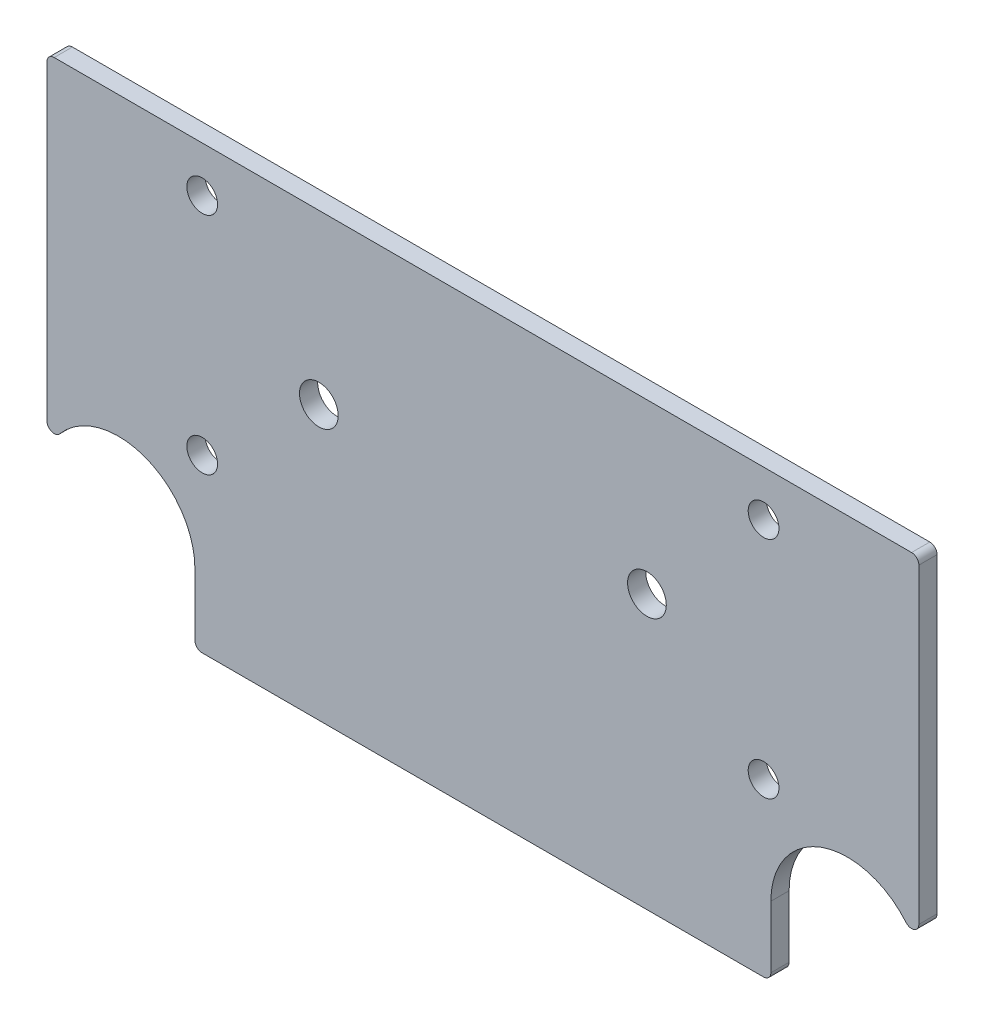
SolidWorks part; units mm, degrees
material "PC High Viscosity"
ref_plane "Front Plane" through (0, 0, 0) normal (0, 0, 1) x (1, 0, 0)
ref_plane "Top Plane" through (0, 0, 0) normal (0, 1, 0) x (1, 0, 0)
ref_plane "Right Plane" through (0, 0, 0) normal (1, 0, 0) x (0, 0, -1)
sketch "Sketch1" plane through (0, 0, 0) normal (0, 0, 1) x (1, 0, 0)
  line L0 (127, 0) -> (-127, 0) construction
  line L1 (101.6, -357.1875) -> (101.6, 357.1875) construction
  line L2 (152.4, 0) -> (152.4, 357.1875) construction
  line L3 (-101.6, -357.1875) -> (-101.6, 357.1875) construction
  line L4 (-152.4, -357.1875) -> (-152.4, 357.1875) construction
  line L5 (101.6, 59.0332) -> (-101.6, 262.2332) construction
  line L6 (101.6, 94.9543) -> (-101.6, 298.1543) construction
  line L7 (0, 196.5543) -> (0, 160.6332) construction
  line L8 (0, 178.5938) -> (152.4, 178.5938) construction
  line L9 (105.003, 12.7) -> (-105.003, 12.7) construction
  line L10 (105.003, -12.7) -> (-105.003, -12.7) construction
  line L11 (-101.6, 59.0332) -> (101.6, 262.2332) construction
  line L12 (-101.6, 94.9543) -> (101.6, 298.1543) construction
  line L13 (152.4, 0) -> (152.4, -357.1875) construction
  line L14 (-101.6, -94.9543) -> (101.6, -298.1543) construction
  line L15 (-101.6, -59.0332) -> (101.6, -262.2332) construction
  line L16 (101.6, -94.9543) -> (-101.6, -298.1543) construction
  line L17 (101.6, -59.0332) -> (-101.6, -262.2332) construction
  line L18 (-179.07, -25.4) -> (-179.07, 128.4583)
  line L19 (-179.07, 128.4583) -> (179.07, 128.4583)
  line L20 (179.07, 128.4583) -> (179.07, -25.4)
  line L21 (179.07, -25.4) -> (153.67, -25.4)
  line L22 (153.67, -25.4) -> (153.67, -1.27)
  line L23 (100.33, -1.27) -> (100.33, -25.4)
  line L24 (100.33, -25.4) -> (-100.33, -25.4)
  line L25 (-100.33, -25.4) -> (-100.33, -1.27)
  line L26 (-153.67, -1.27) -> (-153.67, -25.4)
  line L27 (-179.07, -25.4) -> (-153.67, -25.4)
  circle A0 centre (-127, 0) radius 25.4 construction
  circle A1 centre (127, 0) radius 25.4 construction
  circle A2 centre (-127, 357.1875) radius 25.4 construction
  circle A3 centre (127, 357.1875) radius 25.4 construction
  arc A4 (100.33, -1.27) -> (153.67, -1.27) centre (127, -1.27) cw
  arc A5 (-100.33, -1.27) -> (-153.67, -1.27) centre (-127, -1.27) ccw
  circle A6 centre (96.139, 108.1383) radius 5.461 construction
  point P23 (0, 178.5938)
  point P33 (101.6, 0)
  point P37 (-152.4, 0)
  point P38 (-101.6, 0)
  point P53 (127, 25.4)
  point P54 (127, 25.4)
  dimension "D2" = 50.8
  dimension "D7" = 26.67
  dimension "D9" = 25.4
  dimension "D10" = 10.922
  dimension "D1" = 254
  dimension "D3" = 357.1875
  dimension "D4" = 25.4
  dimension "D5" = 45
  dimension "D6" = 25.4
  dimension "D8" = 25.4
  dimension "D11" = 20.32
extrude "Boss-Extrude1" add sketch "Sketch1" along normal blind 6.35
sketch "Sketch7" plane through (0, 0, 0) normal (0, 0, -1) x (-1, 0, 0)
  line L0 (-151.892, 128.4583) -> (-151.892, 8.3048)
  line L1 (-152.4, 0) -> (-152.4, 357.1875) construction
  line L2 (-179.07, 128.4583) -> (179.07, 128.4583) construction
  line L3 (0, -25.4) -> (0, 128.4583) construction
  line L4 (100.33, -25.4) -> (-100.33, -25.4) construction
  line L5 (-151.892, 128.4583) -> (-179.07, 128.4583)
  line L6 (-179.07, 128.4583) -> (-179.07, -25.4)
  line L7 (-179.07, -25.4) -> (-153.67, -25.4)
  line L8 (-153.67, -25.4) -> (-153.67, -1.27)
  line L9 (153.67, -25.4) -> (153.67, -1.27)
  line L10 (179.07, -25.4) -> (153.67, -25.4)
  line L11 (179.07, 128.4583) -> (179.07, -25.4)
  line L12 (151.892, 128.4583) -> (179.07, 128.4583)
  line L13 (151.892, 128.4583) -> (151.892, 8.3048)
  arc A0 (-100.33, -1.27) -> (-153.67, -1.27) centre (-127, -1.27) ccw construction
  arc A1 (-153.67, -1.27) -> (-151.892, 8.3048) centre (-127, -1.27) cw
  arc A2 (153.67, -1.27) -> (151.892, 8.3048) centre (127, -1.27) ccw
  point P23 (0, 0)
  point P24 (0, 0)
  dimension "D1" = 0.508
extrude "Cut-Extrude1" cut sketch "Sketch7" against normal through all
hole_wizard "27/64 (0.42188) Diameter Hole1" positions "Sketch2" profile "Sketch3" hole size "27/64" standard "ANSI Inch" end condition through all
sketch "Sketch2" plane through (0, 0, 6.35) normal (0, 0, 1) x (1, 0, 0)
  line L0 (-127, 0) -> (-127, 128.4583) construction
  line L1 (-179.07, 128.4583) -> (179.07, 128.4583) construction
  line L2 (0, 128.4583) -> (0, -25.4) construction
  line L3 (100.33, -25.4) -> (-100.33, -25.4) construction
  line L4 (-101.6, -357.1875) -> (-101.6, 357.1875) construction
  point P0 (-97.79, 34.29)
  point P2 (-97.79, 112.5833)
  point P19 (97.79, 34.29)
  point P22 (97.79, 112.5833)
  point P25 (0, 0)
  point P26 (0, 0)
  point P27 (0, 0)
  point P28 (0, 0)
  point P29 (0, 0)
  dimension "D1" = 15.875
  dimension "D2" = 3.81
  dimension "D3" = 34.29
sketch "Sketch3" plane through (-97.79, 34.29, 6.35) normal (1, 0, 0) x (0, -1, 0)
  line L0 (0, 0) -> (0, 6.35)
  line L1 (0, 6.35) -> (5.3579, 6.35)
  line L2 (5.3579, 6.35) -> (5.3579, 0)
  line L5 (5.3579, 0) -> (0, 0)
  line L11 (0, -6.35) -> (0, 107.95) construction
  dimension "Thru Hole Dia." = 10.7158
  dimension "Thru Hole Depth" = 6.35
fillet "Fillet1" radius 2.54 6 edges at (100.33, -25.4, 3.175) (-100.33, -25.4, 3.175) (-151.892, 8.3048, 3.175) (-151.892, 128.4583, 3.175) (151.892, 128.4583, 3.175) (151.892, 8.3048, 3.175)
hole_wizard "1/2 Clearance Hole1" positions "Sketch4" profile "Sketch5" hole size "1/2" standard "ANSI Inch" end condition through all
sketch "Sketch4" plane through (0, 0, 6.35) normal (0, 0, 1) x (1, 0, 0)
  line L1 (0, 0) -> (0, 160.6332) construction
  line L2 (127, 0) -> (-127, 0) construction
  line L4 (105.003, 12.7) -> (-105.003, 12.7) construction
  line L5 (101.6, -357.1875) -> (101.6, 357.1875) construction
  circle A0 centre (57.15, 69.85) radius 12.7 construction
  point P0 (57.15, 69.85)
  point P18 (-57.15, 69.85)
  dimension "D1" = 25.4
  dimension "D2" = 57.15
  dimension "D3" = 44.45
sketch "Sketch5" plane through (57.15, 69.85, 6.35) normal (1, 0, 0) x (0, -1, 0)
  line L0 (0, 0) -> (0, 6.35)
  line L1 (0, 6.35) -> (6.7462, 6.35)
  line L2 (6.7462, 6.35) -> (6.7462, 0)
  line L5 (6.7462, 0) -> (0, 0)
  line L11 (0, -6.35) -> (0, 107.95) construction
  dimension "Thru Hole Dia." = 13.4925
  dimension "Thru Hole Depth" = 6.35
sketch "Sketch6" plane through (0, 0, 6.35) normal (0, 0, 1) x (1, 0, 0)
  line L0 (-127, 128.4583) -> (-127, 25.4) construction
  line L1 (149.352, 128.4583) -> (-149.352, 128.4583) construction
  arc A1 (-100.33, -1.27) -> (-153.67, -1.27) centre (-127, -1.27) ccw construction
  point P4 (-127, 25.4)
  point P7 (-117.8622, 23.7857)
ref_plane "Plane1" through (-127, 0, 0) normal (1, 0, 0) x (0, 0, -1)
